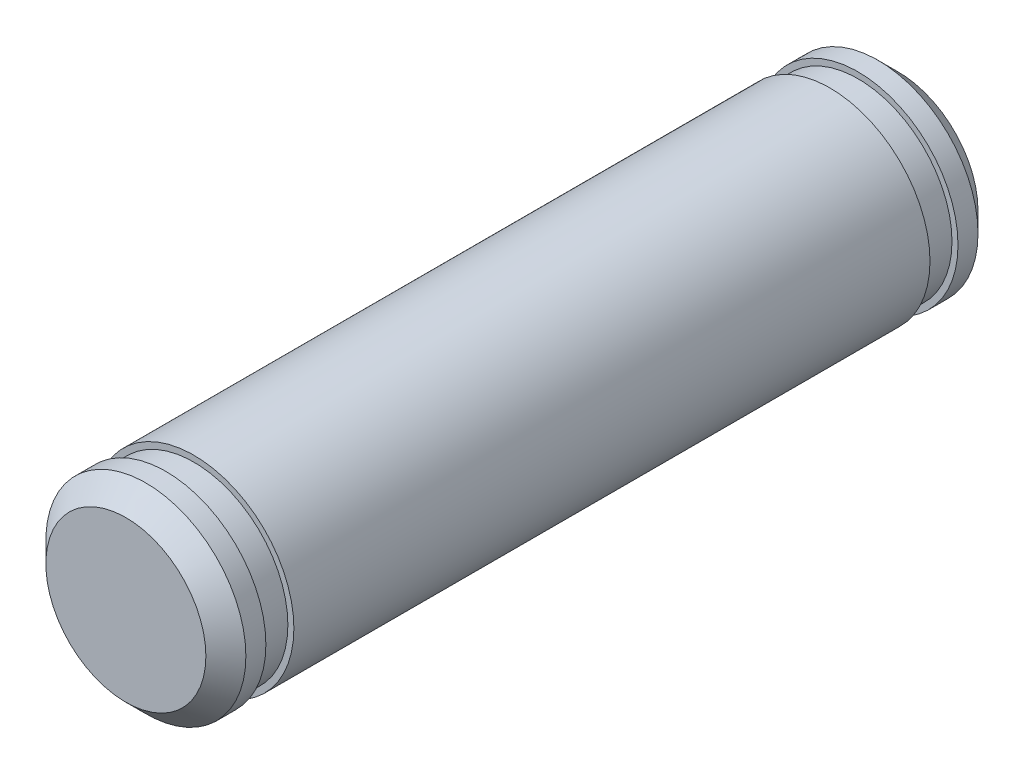
SolidWorks part; units mm, degrees
material "Chromowa stal nierdzewna"
ref_plane "Płaszczyzna przednia" through (0, 0, 0) normal (0, 0, 1) x (1, 0, 0)
ref_plane "Płaszczyzna górna" through (0, 0, 0) normal (0, 1, 0) x (1, 0, 0)
ref_plane "Płaszczyzna prawa" through (0, 0, 0) normal (1, 0, 0) x (0, 0, -1)
sketch "Szkic1" plane through (0, 0, 0) normal (0, 0, 1) x (1, 0, 0)
  circle A0 centre (0, 0) radius 2.5
  dimension "D1" = 5
extrude "Dodanie-wyciągnięcie1" add sketch "Szkic1" along normal blind 19.3
sketch "Szkic2" plane through (0, 0, 19.3) normal (0, 0, 1) x (1, 0, 0)
  circle A0 centre (0, 0) radius 2.5
  circle A1 centre (0, 0) radius 2.35
  dimension "D1" = 5
  dimension "D2" = 4.7
extrude "Wytnij-wyciągnięcie1" cut sketch "Szkic2" against normal blind 0.7 from offset 1 offset against normal yes
extrude "Wytnij-wyciągnięcie2" cut sketch "Szkic2<2>" along normal blind 0.7 from offset 18.3 offset against normal yes
sketch "Szkic2<2>" plane through (0, 0, 19.3) normal (0, 0, 1) x (1, 0, 0) same geometry as "Szkic2"
chamfer "Sfazowanie1" distance 0.5 angle 45 2 edges at (2.5, 0, 0) (2.5, 0, 19.3)
